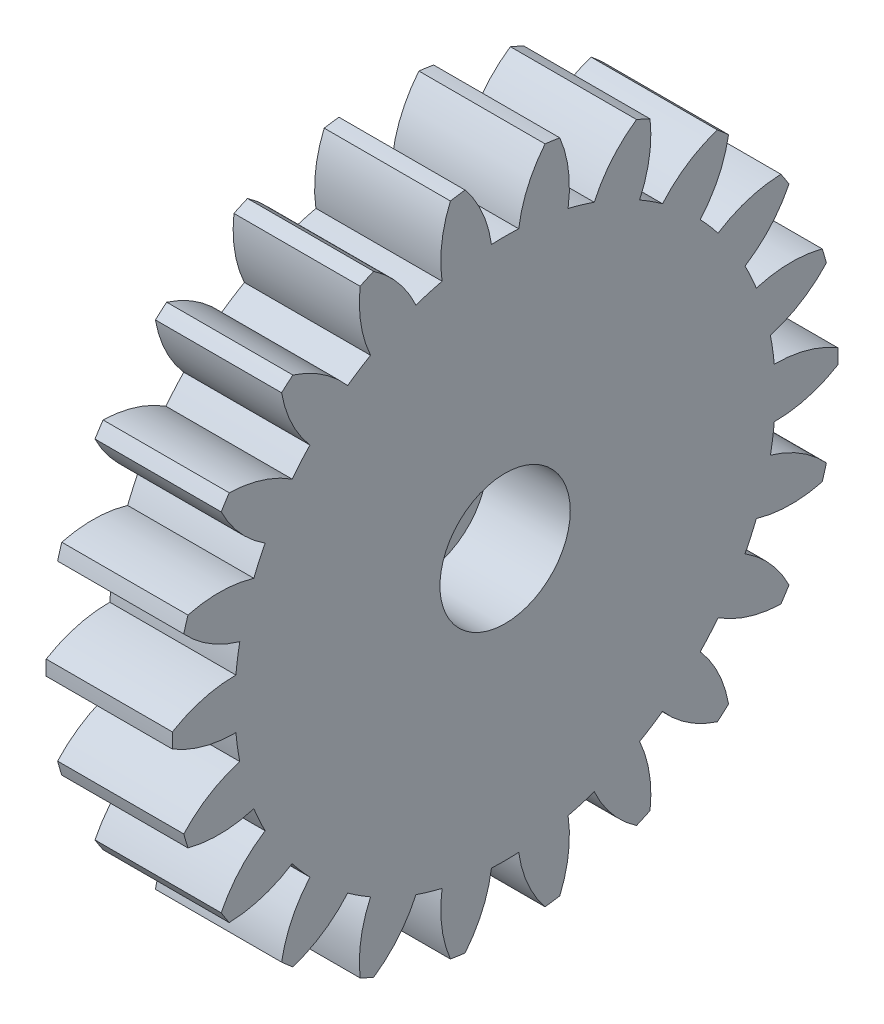
SolidWorks part; units mm, degrees
ref_plane "Plane1" through (0, 0, 0) normal (0, 0, 1) x (1, 0, 0)
ref_plane "Plane2" through (0, 0, 0) normal (0, 1, 0) x (1, 0, 0)
ref_plane "Plane3" through (0, 0, 0) normal (1, 0, 0) x (0, 0, -1)
sketch "HoldingSke" plane through (0, 0, 0) normal (0, 1, 0) x (1, 0, 0)
  line L0 (0, 0) -> (0.9272, -0.3746)
  line L1 (-15, 0) -> (100, 0) construction
  line L2 (0, 0) -> (-2.1039, 2.3779)
  line L3 (0, 0) -> (-11.863, 4.5341)
  line L4 (0, 0) -> (8.0072, 3.2351)
  line L5 (0, 0) -> (-46.8476, -17.4728)
  line L6 (0, 0) -> (-3.7718, -2.5448)
  line L7 (-2.1039, 2.3779) -> (8.6586, 51.2059)
  line L8 (-76.2, 54.61) -> (-75.5, 54.61)
  line L9 (-71.009, 38.7566) -> (-53.1078, 45.2721)
  line L10 (-76.2, 71.12) -> (104.1128, 71.12)
  line L11 (0, 0) -> (-4.55, 0)
  line L12 (-76.2, 101.6) -> (-76.162, 101.6)
  line L13 (24.9733, 27.94) -> (52.9518, 28.4284)
  line L14 (24.9733, 27.94) -> (24.9743, 27.94)
  line L15 (24.9733, 27.94) -> (100.4006, 29.5858)
  line L16 (-63.627, -1) -> (-12.827, -1)
  circle A0 centre (0, 0) radius 2
  circle A1 centre (0, 0) radius 9.749
  circle A2 centre (0, 0) radius 37.5
  circle A3 centre (0, 0) radius 2
  dimension "Num_teeth" = 22
  dimension "Pitch_radius" = 180.3128
  dimension "Width" = 4.55
  dimension "Thickness" = 4.55
sketch "BasProSke" plane through (0, 0, 0) normal (0, 1, 0) x (1, 0, 0)
  line L0 (-10, 0) -> (60, 0) construction
  line L1 (0, 0) -> (0, 12)
  line L2 (0, 0) -> (4.55, 0)
  line L3 (4.55, 0) -> (4.55, 12)
  line L4 (4.55, 12) -> (0, 12)
  dimension "Thickness" = 4.55
  dimension "Diameter" = 24
revolve "Base-Revolve" add sketch "BasProSke" angle 360 about L0
sketch "TooCutSke" plane through (0, 0, 0) normal (1, 0, 0) x (0, 0, -1)
  line L1 (0, 0) -> (0, 107) construction
  line L2 (0, 0) -> (-0.8512, 10.967) construction
  line L3 (0, 0) -> (-3.1242, 21.7296) construction
  line L4 (-0.8512, 10.967) -> (-1.5621, 10.8648) construction
  arc A0 (0.491, 9.7366) -> (-0.491, 9.7366) centre (0, 0) ccw
  arc A1 (1.4609, 11.9363) -> (-1.4609, 11.9363) centre (0, 0) ccw
  circle A2 centre (0, 0) radius 11 construction
  circle A3 centre (0, 0) radius 10.3366 construction
  arc A4 (-0.491, 9.7366) -> (-1.4609, 11.9363) centre (-4.8488, 9.1288) ccw
  arc A5 (1.4609, 11.9363) -> (0.491, 9.7366) centre (4.8488, 9.1288) ccw
extrude "ToothCut" cut sketch "TooCutSke" along normal through all
fillet "Breaks" [suppressed] radius 0.02 tangent propagation no
fillet "RootFillets" [suppressed] radius 0.251
pattern_circular "TeethCuts" count 22 every 16.364 about axis through (-10, 0, 0) along (1, 0, 0) of "ToothCut", "RootFillets", "Breaks"
sketch "HubNeaOneSke" plane through (0, 0, 0) normal (-1, 0, 0) x (0, 0, 1)
  circle A0 centre (0, 0) radius 9.749
  dimension "Diameter" = 19.498
extrude "HubNearOne" [suppressed] add sketch "HubNeaOneSke" along normal blind 45.4501
sketch "HubNeaBotSke" plane through (0, 0, 0) normal (-1, 0, 0) x (0, 0, 1)
  circle A0 centre (0, 0) radius 9.749
  dimension "Diameter" = 19.498
extrude "HubNearBoth" [suppressed] add sketch "HubNeaBotSke" along normal blind 22.725
ref_plane "FarPln" through (4.55, 0, 0) normal (1, 0, 0) x (0, 0, -1)
sketch "HubFarSke" plane through (4.55, 0, 0) normal (1, 0, 0) x (0, 0, -1)
  circle A0 centre (0, 0) radius 9.749
  dimension "Diameter" = 19.498
extrude "HubFar" [suppressed] add sketch "HubFarSke" along normal blind 22.725
sketch "BorSke" plane through (0, 0, 0) normal (1, 0, 0) x (0, 0, -1)
  circle A0 centre (0, 0) radius 1.35
  dimension "Diameter" = 2.7
extrude "Bore" cut sketch "BorSke" along normal mid plane 100.0001
sketch "KeySke" plane through (0, 0, 0) normal (1, 0, 0) x (0, 0, -1)
  line L0 (-0.8, 0) -> (-0.8, 2.7)
  line L1 (-0.8, 2.7) -> (0.8, 2.7)
  line L2 (0.8, 2.7) -> (0.8, 0)
  line L3 (0, 0) -> (0, 34) construction
  line L4 (-0.8, 0) -> (0.8, 0)
  dimension "Width" = 1.6
extrude "Keyway" [suppressed] cut sketch "KeySke" along normal mid plane 100.0001
pattern_circular "Keyway2" [suppressed] count 2 every 90 about axis through (-10, 0, 0) along (1, 0, 0) reverse direction yes
sketch "Sketch1" plane through (0, 0, 0) normal (-1, 0, 0) x (0, 0, 1)
  circle A0 centre (0, 0) radius 4
  circle A1 centre (0, 0) radius 6
  circle A2 centre (0, 0) radius 1.35 construction
  circle A3 centre (0, 0) radius 1.35
  dimension "D1" = 8
  dimension "D2" = 12
extrude "Boss-Extrude1" add sketch "Sketch1" along normal blind 4 contours A0 region at (0, 0, -3.8869)
extrude "Boss-Extrude2" add sketch "Sketch1<4>" along normal blind 1 contours A1 A0 region at (0, 0, -5.8303)
sketch "Sketch1<4>" plane through (0, 0, 0) normal (-1, 0, 0) x (0, 0, 1) same geometry as "Sketch1"
sketch "Sketch2" plane through (4.55, 0, 0) normal (1, 0, 0) x (0, 0, -1)
  circle A0 centre (0, 0) radius 2.35
  circle A1 centre (0, 0) radius 4.35
  dimension "D1" = 4.7
  dimension "D2" = 2
extrude "Boss-Extrude3" [suppressed] add sketch "Sketch2" along normal blind 2.5
fillet "Fillet1" [suppressed] radius 0.5
extrude "Cut-Extrude1" cut sketch "Sketch2<2>" against normal blind 3 contours A0 region at (4.55, 0, 0)
sketch "Sketch2<2>" plane through (4.55, 0, 0) normal (1, 0, 0) x (0, 0, -1) same geometry as "Sketch2"
equation "' \"Module@HoldingSke\" = 6.35"
equation "' \"Num_teeth@HoldingSke\" = 12"
equation "' \"Ap@HoldingSke\" =  20"
equation "' \"Ap@HoldingSke\" = 20"
equation "' \"Width@HoldingSke\" = 0.5 * 25.4"
equation "' \"Hub_dia@HoldingSke\"= 1 * 25.4"
equation "' \"Hub_dia@HoldingSke\" = 1 * 25.4"
equation "' \"Overall_len@HoldingSke\" = 1.0 * 25.4"
equation "' \"Bore@HoldingSke\" = 0.75 * 25.4"
equation "' \"T_dim@HoldingSke\" = 0.1 * 25.4"
equation "' \"Width@KeySke\" = 0.25 * 25.4"
equation "' \"Show_teeth@HoldingSke\" = 13"
equation "' \"Backlash@HoldingSke\" = 0.009 * 25.4"
equation "' \"Addendum_fac@HoldingSke\" = 1.0"
equation "' \"Dedendum_fac@HoldingSke\" = 1.25"
equation "' \"Dedendum_add@HoldingSke\" = 0.00005 * 25.4"
equation "' \"Clearance_fac@HoldingSke\" = 0.25"
equation "\"Pitch@HoldingSke\" = 1 / \"Module@HoldingSke\""
equation "\"Overcut_dia@TooCutSke\" = (\"Num_teeth@HoldingSke\" + 2 * \"Addendum_fac@HoldingSke\") / \"Pitch@HoldingSke\" + 0.002 * 25.4"
equation "\"Pitch_dia@TooCutSke\" = \"Num_teeth@HoldingSke\" / \"Pitch@HoldingSke\""
equation "\"Base_dia@TooCutSke\" = \"Num_teeth@HoldingSke\" / \"Pitch@HoldingSke\" * cos((\"Ap@HoldingSke\"  * 3.14159265 / 180))"
equation "\"Root_dia@TooCutSke\" = (\"Num_teeth@HoldingSke\" + 2) / \"Pitch@HoldingSke\" - 2 * (\"Addendum_fac@HoldingSke\" + \"Dedendum_fac@HoldingSke\") / \"Pitch@HoldingSke\" - \"Dedendum_add@HoldingSke\" * 2"
equation "\"Half_ang@TooCutSke\" = 180 / \"Num_teeth@HoldingSke\""
equation "\"Half_CT@TooCutSke\" = \"Num_teeth@HoldingSke\" / \"Pitch@HoldingSke\" * sin((3.14159265 / 2 / \"Num_teeth@HoldingSke\")) / 2 - 7 * \"Backlash@HoldingSke\" / 4"
equation "\"Flank_rad@TooCutSke\" = \"Num_teeth@HoldingSke\" / \"Pitch@HoldingSke\" / 5"
equation "\"Radius@RootFillets\" = \"Clearance_fac@HoldingSke\" / \"Pitch@HoldingSke\" + \"Dedendum_add@HoldingSke\""
equation "\"Break_rad@Breaks\" = 0.02 / \"Pitch@HoldingSke\""
equation "\"Thickness@HoldingSke\" = \"Width@HoldingSke\""
equation "\"OAL@HoldingSke\" = \"Thickness@HoldingSke\""
equation "\"MHD@HoldingSke\" = (\"Num_teeth@HoldingSke\" + 2) / \"Pitch@HoldingSke\" - 2 * (\"Addendum_fac@HoldingSke\" + \"Dedendum_fac@HoldingSke\")  / \"Pitch@HoldingSke\" - \"Dedendum_add@HoldingSke\" * 2"
equation "\"MBD@HoldingSke\" = (\"Num_teeth@HoldingSke\" + 2) / \"Pitch@HoldingSke\" - 2 * (\"Addendum_fac@HoldingSke\" + \"Dedendum_fac@HoldingSke\")  / \"Pitch@HoldingSke\" - \"Dedendum_add@HoldingSke\" * 2 - 0.002 * 25.4"
equation "\"MHD@HoldingSke\" = ((sgn( \"MHD@HoldingSke\" - \"Hub_dia@HoldingSke\" )-1)*( \"MHD@HoldingSke\" - \"Hub_dia@HoldingSke\" ))/-2+ \"Hub_dia@HoldingSke\""
equation "\"MBD@HoldingSke\" = ((sgn( \"MBD@HoldingSke\" - \"Bore@HoldingSke\" )-1)*( \"MBD@HoldingSke\" - \"Bore@HoldingSke\" ))/-2+ \"Bore@HoldingSke\""
equation "\"OAL@HoldingSke\" = ((sgn( \"OAL@HoldingSke\" - \"Overall_len@HoldingSke\" )+1)*( \"OAL@HoldingSke\" - \"Overall_len@HoldingSke\" ))/2 + \"Overall_len@HoldingSke\" + 0.000002 * 25.4"
equation "\"Num_teeth@TeethCuts\" = int( \"Show_teeth@HoldingSke\" ) + 1"
equation "\"Num_teeth@TeethCuts\" = ((sgn( \"Num_teeth@TeethCuts\" - \"Num_teeth@HoldingSke\" )-1)*( \"Num_teeth@TeethCuts\" - \"Num_teeth@HoldingSke\" ))/-2+ \"Num_teeth@HoldingSke\""
equation "\"Num_teeth@TeethCuts\" = ((sgn( \"Num_teeth@TeethCuts\" - 2.0)+1)*( \"Num_teeth@TeethCuts\" - 2.0))/2 +2.0"
equation "\"Angle@TeethCuts\" = 360.0 / \"Num_teeth@HoldingSke\""
equation "\"Diameter@BasProSke\" = (\"Num_teeth@HoldingSke\" + 2 * \"Addendum_fac@HoldingSke\") / \"Pitch@HoldingSke\""
equation "\"Thickness@BasProSke\"  = \"Thickness@HoldingSke\""
equation "' \"Fillet_rad@BasProSke\" =  \"Thickness@HoldingSke\" * 0.05"
equation "' \"Fillet_rad@BasProSke\" = \"Thickness@HoldingSke\" * 0.05"
equation "\"MHD@HoldingSke\" = ((sgn( \"MHD@HoldingSke\" - \"Root_dia@TooCutSke\" )-1)*( \"MHD@HoldingSke\" - \"Root_dia@TooCutSke\" ))/-2+ \"Root_dia@TooCutSke\""
equation "\"Diameter@HubNeaOneSke\" = \"MHD@HoldingSke\""
equation "\"Length@HubNearOne\" = \"OAL@HoldingSke\" - \"Thickness@BasProSke\""
equation "\"Diameter@HubNeaBotSke\" = \"MHD@HoldingSke\""
equation "\"Length@HubNearBoth\" = ( \"OAL@HoldingSke\" - \"Thickness@BasProSke\" ) / 2.0"
equation "\"Thickness@FarPln\" = \"Thickness@BasProSke\""
equation "\"Diameter@HubFarSke\" = \"MHD@HoldingSke\""
equation "\"Length@HubFar\" = ( \"OAL@HoldingSke\" - \"Thickness@BasProSke\" ) / 2.0"
equation "\"Diameter@BorSke\"=2.7"
equation "\"D1@Bore\" = \"OAL@HoldingSke\" * 2.0"
equation "\"D1@Keyway\" = \"OAL@HoldingSke\" * 2.0"
equation "\"Offset@KeySke\" = \"T_dim@HoldingSke\" + \"MBD@HoldingSke\" / 2.0"
